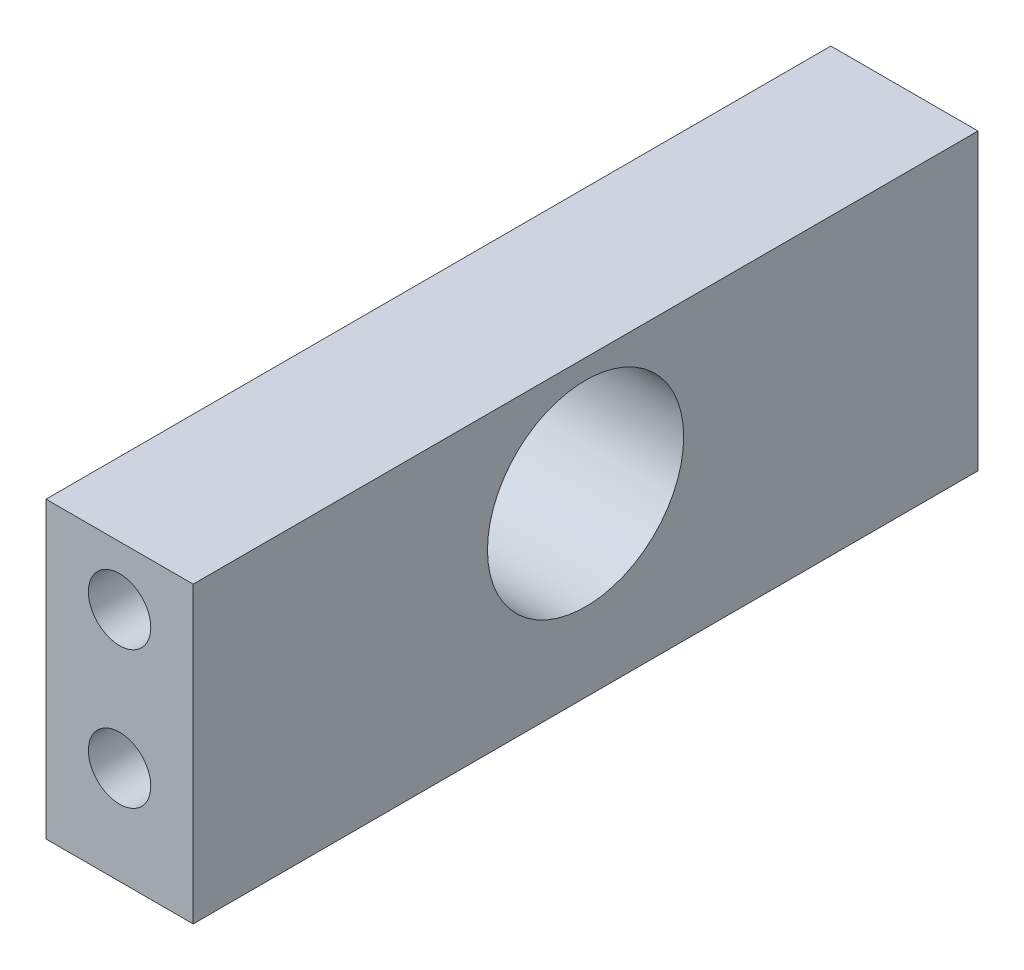
SolidWorks part; units mm, degrees
material "1060 Alloy"
ref_plane "Front Plane" through (0, 0, 0) normal (0, 0, 1) x (1, 0, 0)
ref_plane "Top Plane" through (0, 0, 0) normal (0, 1, 0) x (1, 0, 0)
ref_plane "Right Plane" through (0, 0, 0) normal (1, 0, 0) x (0, 0, -1)
sketch "Sketch1" plane through (0, 0, 0) normal (1, 0, 0) x (0, 0, -1)
  line L1 (-25.4, -9.525) -> (25.4, -9.525)
  line L2 (-25.4, -9.525) -> (-25.4, 9.525)
  line L3 (-25.4, 9.525) -> (25.4, 9.525)
  line L4 (25.4, -9.525) -> (25.4, 9.525)
  line L5 (-25.4, -9.525) -> (25.4, 9.525) construction
  line L6 (-25.4, 9.525) -> (25.4, -9.525) construction
  point P0 (0, 0)
  dimension "D1" = 50.8
  dimension "D2" = 19.05
extrude "Boss-Extrude1" add sketch "Sketch1" along normal blind 9.525
hole_wizard "1/2 (0.5) Diameter Hole1" positions "Sketch9" profile "Sketch8" hole size "1/2" standard "ANSI Inch"
sketch "Sketch9" plane through (9.525, 0, 0) normal (1, 0, 0) x (0, 0, -1)
  line L0 (-25.4, -9.525) -> (25.4, -9.525) construction
  point P0 (0, 1.905)
  dimension "D1" = 11.43
sketch "Sketch8" plane through (9.525, 1.905, 0) normal (0, 1, 0) x (0, 0, -1)
  line L0 (0, 0) -> (0, 73.9195)
  line L1 (0, 73.9195) -> (6.35, 70.104)
  line L2 (6.35, 70.104) -> (6.35, 0)
  line L5 (6.35, 0) -> (0, 0)
  line L10 (0, 73.9195) -> (-6.35, 70.104) construction
  line L11 (0, -6.35) -> (0, 107.95) construction
  dimension "Hole Dia." = 12.7
  dimension "Hole Depth" = 70.104
  dimension "Drill Angle" = 118
hole_wizard "#10-32 Tapped Hole1" positions "Sketch11" profile "Sketch10" tap size "#10-32" standard "ANSI Inch"
sketch "Sketch11" plane through (-0.103, -5.3339, 25.4) normal (0, 0, -1) x (-1, 0, 0)
  line L0 (-9.628, 14.8589) -> (-0.103, 14.8589) construction
  line L2 (-9.628, -4.1911) -> (-0.103, -4.1911) construction
  line L3 (-9.628, 14.8589) -> (-0.103, 14.8589) construction
  point P0 (-4.8655, 2.1589)
  point P2 (-4.8655, 11.0489)
  point P6 (-4.8655, 14.8589)
  dimension "D1" = 0
  dimension "D2" = 0
  dimension "D3" = 3.81
  dimension "D4" = 6.35
sketch "Sketch10" plane through (4.7625, -3.175, 25.4) normal (1, 0, 0) x (0, -1, 0)
  line L0 (0, 0) -> (0, 13.1513)
  line L1 (0, 13.1513) -> (2.0193, 11.938)
  line L2 (2.0193, 11.938) -> (2.0193, 0)
  line L5 (2.0193, 0) -> (0, 0)
  line L10 (0, 13.1513) -> (-2.0193, 11.938) construction
  line L11 (0, -6.35) -> (0, 107.95) construction
  dimension "Tap Drill Dia." = 4.0386
  dimension "Tap Drill Depth" = 11.938
  dimension "Drill Angle" = 118
cosmetic thread "Hole Thread1" parameters "D1"=9.652, "D2"=4.826
cosmetic thread "Hole Thread2" parameters "D1"=9.652, "D2"=4.826
